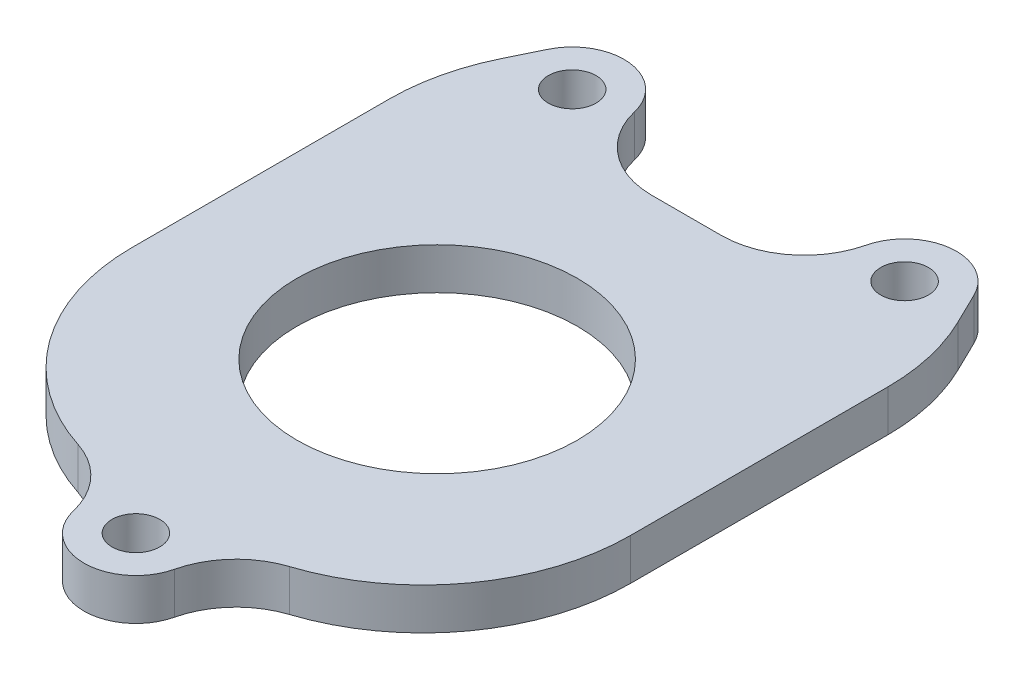
SolidWorks part; units mm, degrees
material "PETG"
ref_plane "Спереди" through (0, 0, 0) normal (0, 0, 1) x (1, 0, 0)
ref_plane "Сверху" through (0, 0, 0) normal (0, 1, 0) x (1, 0, 0)
ref_plane "Справа" through (0, 0, 0) normal (1, 0, 0) x (0, 0, -1)
sketch "Эскиз1" plane through (0, 0, 0) normal (0, 1, 0) x (1, 0, 0)
  line L1 (12, 12) -> (-12, 12)
  line L2 (12, 12) -> (12, -12)
  line L3 (12, -12) -> (-12, -12)
  line L4 (-12, 12) -> (-12, -12)
  line L5 (12, 12) -> (-12, -12) construction
  line L6 (12, -12) -> (-12, 12) construction
  circle A0 centre (0, 0) radius 9.5 construction
  dimension "D1" = 19
  dimension "D3" = 24
  dimension "D2" = 24
extrude "Бобышка-Вытянуть1" add sketch "Эскиз1" along normal blind 2
sketch "Эскиз2" plane through (0, 2, 0) normal (0, 1, 0) x (1, 0, 0)
  line L0 (0, 0) -> (0, -50000) construction
  line L1 (-12, -12) -> (12, -12) construction
  line L2 (-6.3246, -12) -> (6.3246, -12)
  line L3 (-12, 12) -> (-10.2472, 15.5955)
  line L8 (12, 12) -> (-12, 12) construction
  line L10 (-12, 12) -> (-1.6754, 12)
  line L11 (12, 12) -> (1.6754, 12)
  line L12 (12, 12) -> (10.2472, 15.5955)
  circle A0 centre (0, -14.5) radius 1.15
  arc A1 (-2.4325, -15.0769) -> (2.4325, -15.0769) centre (0, -14.5) ccw
  arc A2 (-6.3246, -12) -> (-2.4325, -15.0769) centre (-6.3246, -16) cw
  arc A3 (6.3246, -12) -> (2.4325, -15.0769) centre (6.3246, -16) ccw
  circle A5 centre (-8, 14.5) radius 1.15
  arc A10 (-5.5675, 15.0769) -> (-10.2472, 15.5955) centre (-8, 14.5) ccw
  arc A11 (-5.5675, 15.0769) -> (-1.6754, 12) centre (-1.6754, 16) ccw
  circle A12 centre (8, 14.5) radius 1.15
  arc A13 (5.5675, 15.0769) -> (1.6754, 12) centre (1.6754, 16) cw
  arc A14 (5.5675, 15.0769) -> (10.2472, 15.5955) centre (8, 14.5) cw
  dimension "D1" = 2.3
  dimension "D2" = 5
  dimension "D3" = 4
  dimension "D4" = 2.3
  dimension "D5" = 5
  dimension "D6" = 16
  dimension "D7" = 4
extrude "Бобышка-Вытянуть2" add sketch "Эскиз2" against normal up to surface (2 mm away) up to face at (0, 0, 0)
fillet "Скругление1" radius 10 2 edges at (12, 1, 12) (-12, 1, 12)
sketch "Эскиз3" plane through (0, 2, 0) normal (0, 1, 0) x (1, 0, 0)
  circle A0 centre (0, 0) radius 6.75
  dimension "D1" = 13.5
extrude "Вырез-Вытянуть1" cut sketch "Эскиз3" against normal up to surface (2 mm away) up to face at (0, 0, -3.4215)
fillet "Скругление2" radius 10 2 edges at (12, 1, -12) (-12, 1, -12)
